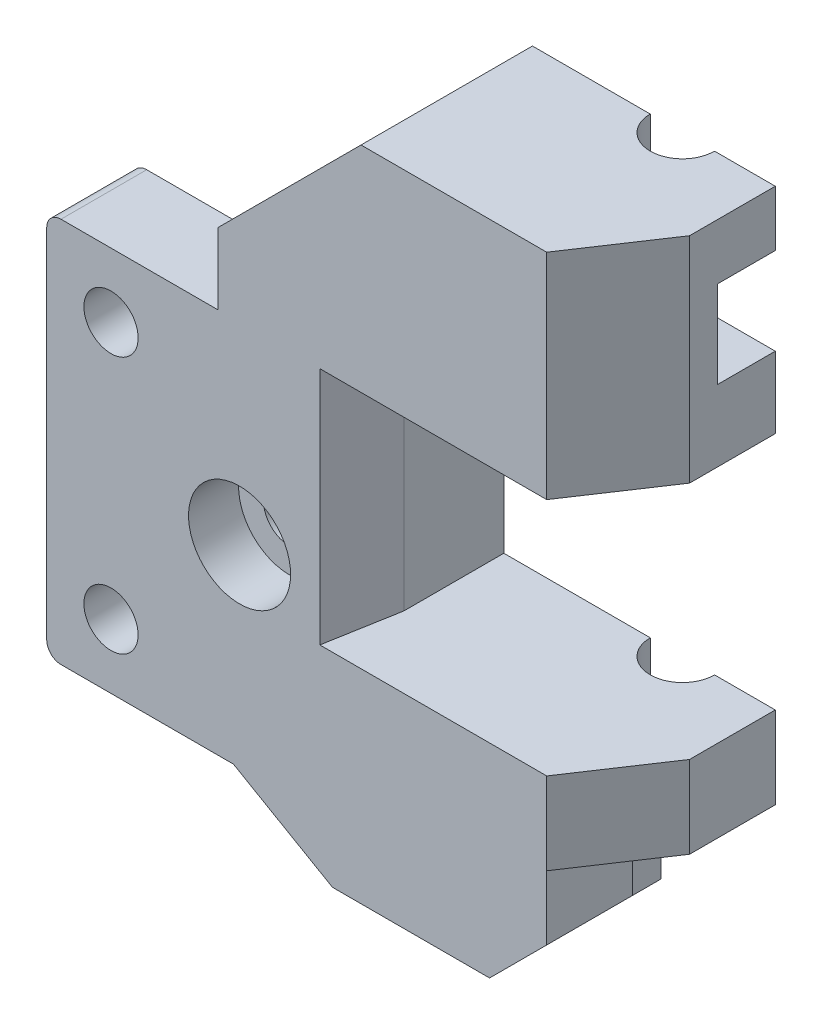
SolidWorks part; units mm, degrees
note: The reader was unsure of these and kept them because the rebuilt part matched: shared geometry of "Sketch11<5>".
material "ABS"
ref_plane "Front Plane" through (0, 0, 0) normal (0, 0, 1) x (1, 0, 0)
ref_plane "Top Plane" through (0, 0, 0) normal (0, 1, 0) x (1, 0, 0)
ref_plane "Right Plane" through (0, 0, 0) normal (1, 0, 0) x (0, 0, -1)
sketch "Sketch2" plane through (0, 0, 0) normal (0, 0, 1) x (1, 0, 0)
  line L1 (1, 0) -> (20, 0)
  line L2 (0, 1) -> (0, 26)
  line L3 (1, 27) -> (20, 27)
  line L4 (20, 0) -> (20, 27)
  arc A0 (1, 0) -> (0, 1) centre (1, 1) cw
  arc A1 (1, 27) -> (0, 26) centre (1, 26) ccw
  point P3 (20, 0)
  point P6 (0, 0)
  point P10 (0, 27)
  dimension "D2" = 1
  dimension "D1" = 27
  dimension "D3" = 20
extrude "Boss-Extrude1" add sketch "Sketch2" along normal blind 6
sketch "Sketch3" plane through (0, 0, 0) normal (0, 0, 1) x (1, 0, 0)
  line L0 (4.5, 4.5) -> (4.5, 22.5) construction
  line L1 (1, 0) -> (20, 0) construction
  line L2 (0, 26) -> (0, 1) construction
  line L3 (3.5, 15.067) -> (3.5, 11.933) construction
  line L4 (0, 26) -> (0, 1) construction
  line L5 (12, 27) -> (12, 22.5)
  line L6 (20, 27) -> (1, 27) construction
  line L7 (20, 4.5) -> (15.2819, 4.5)
  line L8 (20, 0) -> (20, 27) construction
  line L9 (20, 0) -> (20, 27)
  line L10 (20, 0) -> (20, 27) construction
  line L11 (1, 0) -> (20, 0) construction
  line L12 (7.2883, 0) -> (1, 0)
  circle A0 centre (4.5, 22.5) radius 2.15 construction
  circle A1 centre (4.5, 4.5) radius 2.15 construction
  circle A2 centre (4.5, 22.5) radius 7.5
  circle A3 centre (4.5, 4.5) radius 7.5
  arc A4 (11.5317, 7.1087) -> (3.5, 11.933) centre (4.5, 4.5) ccw construction
  arc A5 (11.5317, 7.1087) -> (15.2819, 4.5) centre (15.2819, 8.5) ccw
  arc A6 (15.2819, 4.5) -> (10.7081, 1.9252) centre (15.2819, -0.8499) ccw
  arc A7 (7.2883, 0) -> (10.7081, 1.9252) centre (7.2883, 4) ccw
  point P28 (12, 4.5)
  point P36 (10, 0)
  line M13 (20, 27) -> (20, 0)
  line M14 (20, 0) -> (1, 0)
  line M18 (1, 27) -> (20, 27)
  dimension "D1" = 4.3
  dimension "D2" = 4.3
  dimension "D6" = 15
  dimension "D7" = 15
  dimension "D9" = 4
  dimension "D10" = 10
  dimension "D11" = 4
  dimension "D3" = 18
  dimension "D4" = 4.5
  dimension "D5" = 4.5
  dimension "D8" = 3.5
extrude "Boss-Extrude3" add sketch "Sketch3" against normal blind 6 contours A3 L0 A2 M18 M13 M14
sketch "Sketch8" plane through (0, 0, 6) normal (0, 0, 1) x (1, 0, 0)
  line L0 (4.5, 13.5) -> (13.5, 13.5) construction
  line L6 (12, 27) -> (12, 22.5)
  line L7 (12, 27) -> (12, 22.5)
  line L8 (20, 27) -> (12, 27)
  line L9 (20, 4.5) -> (20, 27)
  line L10 (15.2819, 4.5) -> (20, 4.5)
  line L11 (0, 16.5) -> (0, 10.5)
  line L12 (0, 16.5) -> (0, 10.5)
  line L13 (20, 27) -> (12, 27)
  line L14 (20, 4.5) -> (20, 27)
  line L15 (15.2819, 4.5) -> (20, 4.5)
  arc A3 (11.5317, 7.1087) -> (0, 10.5) centre (4.5, 4.5) ccw
  arc A4 (11.5317, 7.1087) -> (0, 10.5) centre (4.5, 4.5) ccw
  arc A5 (0, 16.5) -> (12, 22.5) centre (4.5, 22.5) ccw
  arc A6 (0, 16.5) -> (12, 22.5) centre (4.5, 22.5) ccw
  arc A7 (11.5317, 7.1087) -> (15.2819, 4.5) centre (15.2819, 8.5) ccw
  arc A8 (11.5317, 7.1087) -> (15.2819, 4.5) centre (15.2819, 8.5) ccw
  point P2 (13.5, 13.5)
  dimension "D2" = 9
  dimension "D1" = 0
hole_wizard "CBORE for #6 Socket Head Cap Screw1" positions "Sketch10" profile "Sketch9" counterbore size "#6" standard "ANSI Inch" end condition through all
sketch "Sketch10" plane through (0, 0, 6) normal (0, 0, 1) x (1, 0, 0)
  point P0 (13.5, 13.5)
sketch "Sketch9" plane through (13.5, 13.5, 6) normal (1, 0, 0) x (0, -1, 0)
  line L0 (0, 0) -> (0, 12)
  line L1 (0, 12) -> (1.8288, 12)
  line L3 (1.8288, 12) -> (1.8288, 3.5052)
  line L4 (1.8288, 3.5052) -> (3.5725, 3.5052)
  line L5 (3.5725, 3.5052) -> (3.5725, 0)
  line L7 (3.5725, 0) -> (0, 0)
  line L11 (0, -6.35) -> (0, 107.95) construction
  dimension "Thru Hole Dia." = 3.6576
  dimension "Thru Hole Depth" = 12
  dimension "C'Bore Dia." = 7.145
  dimension "C'Bore Depth" = 3.5052
hole_wizard "#6 Clearance Hole1" positions "Sketch24" profile "Sketch23" hole size "#6" standard "ANSI Inch"
sketch "Sketch24" plane through (0, 0, 0) normal (0, 0, -1) x (-1, 0, 0)
  point P0 (-4.5, 22.5)
  point P3 (-4.5, 4.5)
sketch "Sketch23" plane through (4.5, 22.5, 0) normal (1, 0, 0) x (0, 1, 0)
  line L0 (0, 0) -> (0, 18.6108)
  line L1 (0, 18.6108) -> (1.8986, 17.47)
  line L2 (1.8986, 17.47) -> (1.8986, 0)
  line L5 (1.8986, 0) -> (0, 0)
  line L10 (0, 18.6108) -> (-1.8986, 17.47) construction
  line L11 (0, -6.35) -> (0, 107.95) construction
  dimension "Hole Dia." = 3.7973
  dimension "Hole Depth" = 17.47
  dimension "Drill Angle" = 118
sketch "Sketch11" plane through (0, 27, 0) normal (0, 1, 0) x (1, 0, 0)
  line L0 (20, 6) -> (32.5, 6)
  line L1 (12, 6) -> (12, -6)
  line L2 (20, -6) -> (35, -6)
  line L3 (39, 0) -> (39, 6)
  line L4 (35, -6) -> (39, 0)
  line L5 (34.75, 6) -> (39, 6)
  line L6 (20, -6) -> (20, 6)
  line L7 (20, 6) -> (12, 6)
  line L8 (12, 6) -> (20, 6) construction
  line L10 (1, 0) -> (1, -6)
  line L11 (1, -6) -> (20, -6)
  line L12 (20, -6) -> (20, 6)
  line L13 (20, 6) -> (12, 6)
  line L16 (1, 0) -> (1, -6)
  line L17 (1, -6) -> (20, -6)
  line L18 (34.75, 6) -> (32.5, 6)
  line L22 (12, 6) -> (12, 0)
  line L23 (12, 6) -> (12, 0)
  line L24 (12, 0) -> (1, 0)
  line L25 (12, 0) -> (1, 0)
  circle A0 centre (32.5, 6) radius 7.5 construction
  circle A1 centre (32.5, 6) radius 2.25
  point P10 (39, -6)
  dimension "D3" = 15
  dimension "D4" = 4.5
  dimension "D2" = 12.5
  dimension "D5" = 6.5
  dimension "D7" = 6
  dimension "D6" = 4
  dimension "D8" = 8
  dimension "D1" = 0
extrude "Boss-Extrude5" add sketch "Sketch11" along normal blind 15
ref_plane "Plane1" through (0, 10.25, 0) normal (0, -1, 0) x (-1, 0, 0)
sketch "Sketch13" plane through (0, 10.25, 0) normal (0, -1, 0) x (-1, 0, 0)
  line L5 (-20, 6) -> (-39, 6)
  line L6 (-20, 6) -> (-39, 6)
  line L7 (-20, -6) -> (-20, 6)
  line L9 (-39, 6) -> (-39, 0)
  line L10 (-39, 0) -> (-35, -6)
  line L11 (-35, -6) -> (-20, -6)
  line L13 (-20, -6) -> (-20, 6)
  line L15 (-39, 6) -> (-39, 0)
  line L16 (-39, 0) -> (-35, -6)
  line L17 (-35, -6) -> (-20, -6)
  dimension "D1" = 0
extrude "Boss-Extrude6" add sketch "Sketch13" along normal up to surface (5.75 mm away) up to face at (18.2307, 4.5, -3.75)
extrude "Cut-Extrude1" cut sketch "Sketch11<5>" against normal offset from surface 2.5 and the other way through all contours A1
sketch "Sketch11<5>" plane through (0, 27, 0) normal (0, 1, 0) x (1, 0, 0) same geometry as "Sketch11"
ref_plane "Plane2" through (0, 32, 0) normal (0, -1, 0) x (-1, 0, 0)
sketch "Sketch14" plane through (0, 32, 0) normal (0, -1, 0) x (-1, 0, 0)
  line L1 (-29.85, -0.55) -> (-24.85, -0.55)
  line L2 (-29.85, -0.55) -> (-29.85, 12.55)
  line L3 (-29.85, 12.55) -> (-24.85, 12.55)
  line L4 (-24.85, -0.55) -> (-24.85, 12.55)
  line L5 (-24.85, 12.55) -> (-9.85, 12.55)
  line L6 (-24.85, 12.55) -> (-24.85, -0.55)
  line L7 (-24.85, -0.55) -> (-9.85, -0.55)
  line L8 (-9.85, 12.55) -> (-9.85, -0.55)
  arc A0 (-34.75, 6) -> (-30.25, 6) centre (-32.5, 6) ccw construction
  arc A1 (-34.75, 6) -> (-30.25, 6) centre (-32.5, 6) ccw construction
  circle A2 centre (-32.5, 6) radius 7.6 construction
  circle A3 centre (-32.5, 6) radius 7.65
  point P10 (-24.85, 6)
  dimension "D1" = 15.2
  dimension "D3" = 13.1
  dimension "D4" = 5
  dimension "D5" = 15
  dimension "D2" = 0.05
extrude "Cut-Extrude2" cut sketch "Sketch14" against normal blind 6.1 contours A3 L6 L3 | A3 L1 L4 | L8 L5 L6 L4 L7
chamfer "Chamfer2" distance 10 angle 45 2 edges at (12, 38.1, -2.725) (12, 42, 0)
sketch "Sketch26" plane through (0, 0, -6) normal (0, 0, -1) x (-1, 0, 0)
  line L0 (-20, 25.3576) -> (-12, 25.3576) construction
  line L1 (-20, 27) -> (-20, 10.25) construction
  line L2 (-12, 27) -> (-12, 22.5) construction
  line L3 (-16, 25.3576) -> (-16, 29.5291) construction
  line L4 (-28.5478, 32) -> (-12, 32) construction
  circle A0 centre (-16, 26) radius 2
  dimension "D1" = 4
  dimension "D2" = 6
extrude "Boss-Extrude10" add sketch "Sketch26" along normal blind 2
chamfer "Chamfer3" distance 5 angle 10 1 edges at (20, 18.625, 6)
sketch "Sketch15" plane through (0, 0, 6) normal (0, 0, 1) x (1, 0, 0)
  line L0 (20, 0) -> (20, -4)
  line L1 (20, -4) -> (13.0718, 0)
  line L2 (1, 0) -> (20, 0) construction
  line L3 (20, -4) -> (31, -4)
  line L4 (35, 0) -> (35, 4.5)
  line L5 (31, -4) -> (35, 0)
  point P6 (35, -4)
  line M12 (1, 0) -> (20, 0)
  line M13 (20, 0) -> (20, 4.5)
  line M14 (20, 4.5) -> (35, 4.5)
  dimension "D1" = 4
  dimension "D2" = 60
extrude "Boss-Extrude7" add sketch "Sketch15" against normal up to surface (6 mm away) contours L3 L4 L0 M14 M13 | L1 L0 M12 up to face at (2.6014, 4.5, 0)
sketch "Sketch17" plane through (0, 0, 0) normal (0, 0, -1) x (-1, 0, 0)
  line L0 (-30.25, 0) -> (-15.8708, 0)
  line L8 (-35, 4.5) -> (-35, 0)
  line L9 (-35, 0) -> (-31, -4)
  line L10 (0, 1) -> (0, 10.5)
  line L11 (-15.2819, 4.5) -> (-35, 4.5)
  line L14 (-31, -0.75) -> (-31, -4)
  line L15 (-31, -4) -> (-20, -4)
  line L16 (-13.0718, 0) -> (-1, 0)
  line L21 (-31, -4) -> (-20, -4)
  line L22 (-20, -4) -> (-13.0718, 0)
  line L23 (-20, -4) -> (-15.4958, -1.3995)
  arc A0 (-15.4958, -1.3995) -> (-15.8708, 0) centre (-15.8708, -0.75) ccw
  arc A1 (-30.25, 0) -> (-31, -0.75) centre (-30.25, -0.75) ccw
  arc A3 (-1, 0) -> (0, 1) centre (-1, 1) ccw
  arc A4 (0, 10.5) -> (-11.5317, 7.1087) centre (-4.5, 4.5) ccw
  arc A6 (-15.2819, 4.5) -> (-11.5317, 7.1087) centre (-15.2819, 8.5) ccw
  arc A7 (-15.2819, 4.5) -> (-11.5317, 7.1087) centre (-15.2819, 8.5) ccw
  dimension "D2" = 0.75
  dimension "D1" = 0
extrude "Boss-Extrude9" add sketch "Sketch17" along normal up to surface (6 mm away) contours L0 A0 L23 L21 L14 A1 up to face at (11.6712, 13.5, -6)
